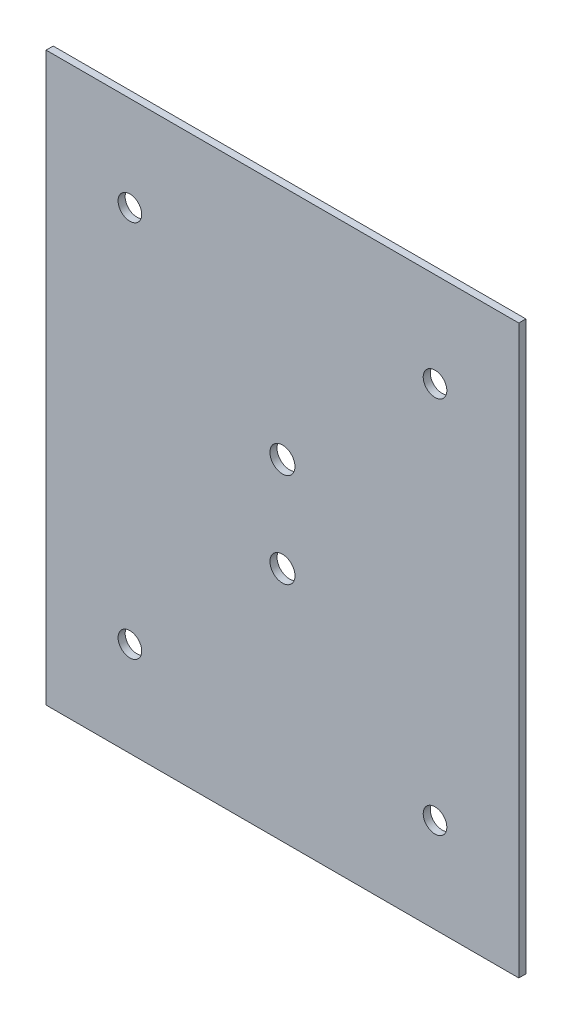
SolidWorks part; units mm, degrees
material "Stainless Steel (ferritic)"
ref_plane "Front Plane" through (0, 0, 0) normal (0, 0, 1) x (1, 0, 0)
ref_plane "Top Plane" through (0, 0, 0) normal (0, 1, 0) x (1, 0, 0)
ref_plane "Right Plane" through (0, 0, 0) normal (1, 0, 0) x (0, 0, -1)
sketch "Sketch1" plane through (0, 0, 0) normal (0, 0, 1) x (1, 0, 0)
  line L1 (0, 0) -> (100, 0)
  line L2 (0, 0) -> (0, 120)
  line L3 (0, 120) -> (100, 120)
  line L4 (100, 0) -> (100, 120)
  dimension "D1" = 120
  dimension "D2" = 100
extrude "Boss-Extrude1" add sketch "Sketch1" along normal blind 1.5
sketch "Sketch2" plane through (0, 0, 0) normal (0, 0, -1) x (-1, 0, 0)
  line L0 (-82.275, 100) -> (-17.725, 100) construction
  line L1 (-17.725, 100) -> (-17.725, 20) construction
  line L2 (-17.725, 20) -> (-82.275, 20) construction
  line L3 (-82.275, 20) -> (-82.275, 100) construction
  line L4 (-82.275, 100) -> (-100, 100) construction
  line L5 (-100, 0) -> (-100, 120) construction
  line L6 (-82.275, 100) -> (-82.275, 120) construction
  line L7 (-100, 120) -> (0, 120) construction
  line L8 (-17.725, 100) -> (-17.725, 120) construction
  line L9 (-17.725, 100) -> (0, 100) construction
  line L10 (0, 120) -> (0, 0) construction
  line L11 (-17.725, 20) -> (0, 20) construction
  line L12 (-17.725, 20) -> (-17.725, 0) construction
  line L13 (0, 0) -> (-100, 0) construction
  line L14 (-82.275, 20) -> (-82.275, 0) construction
  line L15 (-82.275, 20) -> (-100, 20) construction
  circle A0 centre (-82.275, 20) radius 2.5
  circle A1 centre (-17.725, 20) radius 2.5
  circle A2 centre (-17.725, 100) radius 2.5
  circle A3 centre (-82.275, 100) radius 2.5
  dimension "D1" = 5
  dimension "D2" = 17.725
  dimension "D3" = 20
extrude "Cut-Extrude1" cut sketch "Sketch2" against normal blind 1.5
sketch "Sketch4" plane through (0, 0, 1.5) normal (0, 0, 1) x (1, 0, 0)
  line L0 (50, 120) -> (50, 0) construction
  line L1 (0, 0) -> (100, 0)
  line L2 (0, 0) -> (0, 120)
  line L3 (0, 120) -> (100, 120)
  line L4 (100, 0) -> (100, 120)
  line L5 (50, 60) -> (50, 70) construction
  line L6 (50, 60) -> (50, 50) construction
  circle A0 centre (50, 70) radius 2.65
  circle A1 centre (50, 50) radius 2.65
  dimension "D2" = 5.3
  dimension "D3" = 5.3
  dimension "D1" = 20
extrude "Cut-Extrude2" cut sketch "Sketch4" against normal up to surface (1.5 mm away) contours A1 | A0 region at (50, 70, 1.5) region at (50, 50, 1.5) up to face at (79.775, 100, 0)
